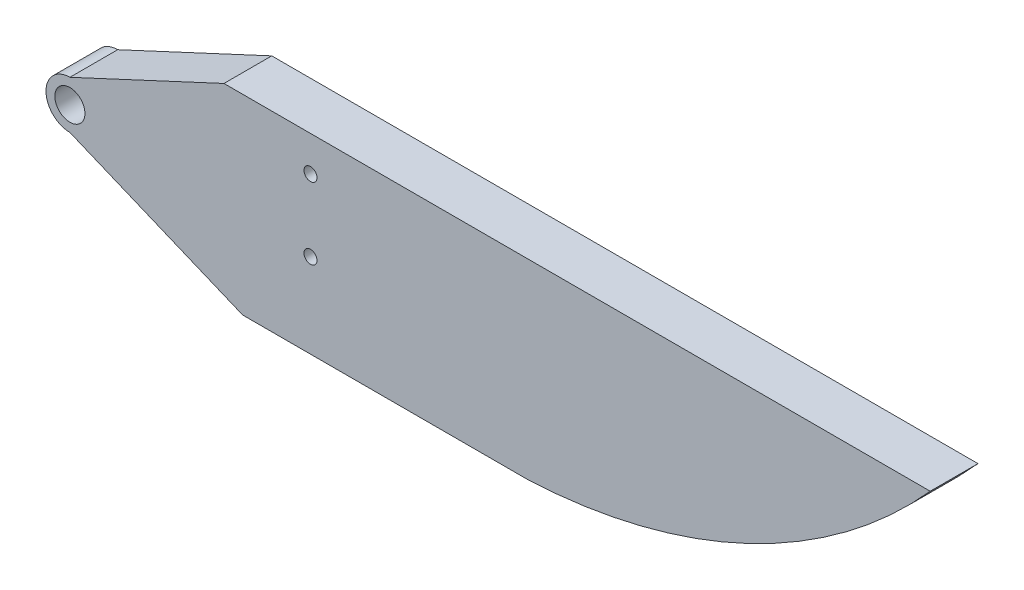
SolidWorks part; units mm, degrees
ref_plane "Front Plane" through (0, 0, 0) normal (0, 0, 1) x (1, 0, 0)
ref_plane "Top Plane" through (0, 0, 0) normal (0, 1, 0) x (1, 0, 0)
ref_plane "Right Plane" through (0, 0, 0) normal (1, 0, 0) x (0, 0, -1)
sketch "Sketch1" plane through (0, 0, 0) normal (0, 0, 1) x (1, 0, 0)
  line L1 (120.65, 25.4) -> (-120.65, 25.4)
  line L2 (120.65, 25.4) -> (120.65, -25.4)
  line L3 (120.65, -25.4) -> (-120.65, -25.4)
  line L4 (-120.65, 25.4) -> (-120.65, -25.4)
  line L5 (120.65, 25.4) -> (-120.65, -25.4) construction
  line L6 (120.65, -25.4) -> (-120.65, 25.4) construction
  point P0 (0, 0)
  dimension "D1" = 241.3
  dimension "D2" = 50.8
extrude "Boss-Extrude1" add sketch "Sketch1" along normal blind 12.7
sketch "Sketch3" plane through (0, 0, 12.7) normal (0, 0, 1) x (1, 0, 0)
  line L0 (0, 0) -> (-120.65, 0) construction
  line L1 (-120.65, 25.4) -> (-120.65, -25.4) construction
  circle A0 centre (-107.95, 0) radius 4
  dimension "D2" = 8
  dimension "D1" = 12.7
extrude "Cut-Extrude1" cut sketch "Sketch3" against normal through all
sketch "Sketch5" plane through (0, 0, 12.7) normal (0, 0, 1) x (1, 0, 0)
  line L0 (-120.65, -25.4) -> (120.65, -25.4) construction
  line L1 (-107.95, -6.35) -> (-62.0461, -25.4)
  line L2 (-107.95, 6.35) -> (-67.0151, 25.4)
  line L3 (120.65, 25.4) -> (-120.65, 25.4) construction
  line L4 (-67.0151, 25.4) -> (-120.65, 25.4)
  line L5 (-120.65, 25.4) -> (-120.65, -25.4)
  line L6 (-120.65, -25.4) -> (-62.0461, -25.4)
  line L7 (120.65, 25.4) -> (120.65, -25.4)
  line L8 (120.65, -25.4) -> (0, -25.4)
  arc A0 (0, -25.4) -> (120.65, 25.4) centre (6.9175, 126.8429) ccw
  arc A2 (-107.95, 6.35) -> (-107.95, -6.35) centre (-107.95, 0) ccw
  point P15 (0, 0)
  point P20 (-67.0151, 25.4)
  point P22 (120.65, 25.4)
  line M3 (-120.65, 25.4) -> (-120.65, -25.4)
  line M4 (-120.65, -25.4) -> (120.65, -25.4)
  line M5 (120.65, -25.4) -> (120.65, 25.4)
  line M6 (120.65, 25.4) -> (-120.65, 25.4)
  dimension "D1" = 152.4
  dimension "D2" = 12.7
extrude "Cut-Extrude2" cut sketch "Sketch5" against normal through all contours A2 L2 L1 M6 M3 M4 | A0 L8 M5 region at (-85.2953, -16.5913, 12.7) region at (93.5193, -10.6939, 12.7)
sketch "Sketch6" plane through (0, 0, 12.7) normal (0, 0, 1) x (1, 0, 0)
  line L0 (-107.95, 0) -> (91.396, 0) construction
  arc A0 (13.8349, -25.4) -> (120.65, 25.4) centre (6.9175, 126.8429) ccw construction
  circle A1 centre (19.05, 0) radius 3.1347
  dimension "D1" = 127
sketch "Sketch7" plane through (0, 0, 0) normal (0, 0, -1) x (-1, 0, 0)
  line L0 (44.0204, -2.9977) -> (44.0204, 16.0523) construction
  point P3 (44.0204, -2.9977)
  point P4 (44.0204, 16.0523)
  dimension "D1" = 19.05
sketch "Sketch8" plane through (0, 0, 0) normal (0, 0, -1) x (-1, 0, 0)
  point P0 (44.0204, 16.0523)
  point P3 (44.0204, -2.9977)
hole_wizard "Tap Drill for #8-32 Tap1" positions "Sketch8" profile "Sketch9" hole size "#8-32" standard "ANSI Inch" end condition through all
sketch "Sketch9" plane through (-44.0204, 16.0523, 0) normal (1, 0, 0) x (0, 1, 0)
  line L0 (0, 0) -> (0, 12.7)
  line L1 (0, 12.7) -> (1.7272, 12.7)
  line L2 (1.7272, 12.7) -> (1.7272, 0)
  line L5 (1.7272, 0) -> (0, 0)
  line L11 (0, -6.35) -> (0, 107.95) construction
  dimension "Thru Hole Dia." = 3.4544
  dimension "Thru Hole Depth" = 12.7
ref_plane "Plane1" through (-114.3, 0, 0) normal (-1, 0, 0) x (0, 0, 1)
sketch "Sketch10" plane through (-114.3, 0, 0) normal (-1, 0, 0) x (0, 0, 1)
  line L0 (0, 0) -> (12.7, 0) construction
  line L1 (12.7, -3.1347) -> (12.7, 3.1347) construction
  circle A0 centre (6.0894, 0) radius 1.905
  dimension "D1" = 3.81
extrude "Cut-Extrude3" cut sketch "Sketch10" against normal blind 5.08
